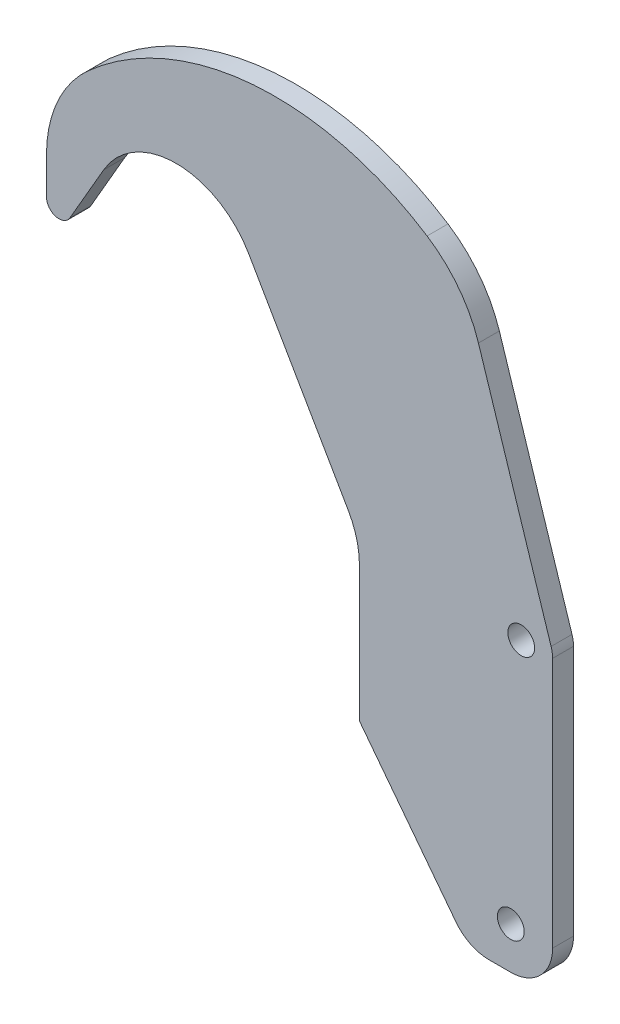
SolidWorks part; units mm, degrees
ref_plane "Front Plane" through (0, 0, 0) normal (0, 0, 1) x (1, 0, 0)
ref_plane "Top Plane" through (0, 0, 0) normal (0, 1, 0) x (1, 0, 0)
ref_plane "Right Plane" through (0, 0, 0) normal (1, 0, 0) x (0, 0, -1)
sketch "Sketch1" plane through (0, 0, 0) normal (0, 0, 1) x (1, 0, 0)
  line L0 (-10.9985, 23.8125) -> (-26.1215, -2.3812) construction
  line L1 (-15.123, -21.4313) -> (15.123, -21.4313) construction
  line L2 (26.1215, -2.3812) -> (10.9985, 23.8125) construction
  line L3 (10.9985, 23.8125) -> (26.1215, -2.3812)
  line L4 (-10.9985, 23.8125) -> (-16.1312, 14.9225)
  line L5 (-19.6859, 15.875) -> (-19.6859, 28.575)
  line L8 (57.15, -6.35) -> (57.15, -44.45)
  line L9 (50.8, -50.8) -> (47.4961, -50.8)
  line L15 (56.9223, -4.895) -> (44.1478, 34.9199)
  line L16 (27.823, -8.7312) -> (27.823, -29.2393)
  line L17 (27.823, -29.2393) -> (42.458, -48.3152)
  circle A0 centre (0, 0) radius 21.4313 construction
  arc A1 (10.9985, 23.8125) -> (-10.9985, 23.8125) centre (0, 17.4625) ccw construction
  arc A2 (-26.1215, -2.3812) -> (-15.123, -21.4313) centre (-15.123, -8.7313) ccw construction
  arc A3 (15.123, -21.4313) -> (26.1215, -2.3812) centre (15.123, -8.7312) ccw construction
  arc A4 (-10.9985, 23.8125) -> (10.9985, 23.8125) centre (0, 17.4625) cw
  arc A5 (26.1215, -2.3812) -> (27.823, -8.7312) centre (15.123, -8.7312) cw
  arc A6 (57.15, -6.35) -> (56.9223, -4.895) centre (52.3875, -6.35) ccw
  arc A9 (-19.6859, 15.875) -> (-16.1312, 14.9225) centre (-17.7809, 15.875) ccw
  arc A10 (50.8, -50.8) -> (57.15, -44.45) centre (50.8, -44.45) ccw
  arc A11 (42.458, -48.3152) -> (47.4961, -50.8) centre (47.4961, -44.45) ccw
  circle A12 centre (50.8, -44.45) radius 2.032
  circle A15 centre (52.3875, -6.35) radius 2.032
  arc A16 (-19.6859, 28.575) -> (44.1478, 34.9199) centre (14.9956, 3.9323) cw
  point P15 (43.8388, -44.45)
  point P26 (30.7767, -35.7857)
  point P29 (47.4961, -44.45)
  point P35 (32.6901, -34.829)
  point P36 (41.1461, -27.7493)
  point P37 (27.823, -29.2393)
  point P39 (27.823, 45.74)
  point P40 (44.1478, 34.9199)
  dimension "D2" = 12.7
  dimension "D3" = 9.525
  dimension "D1" = 42.8625
  dimension "D4" = 30
  dimension "D5" = 1.905
  dimension "D12" = 4.064
  dimension "D9" = 50.8
  dimension "D7" = 42.545
  dimension "D6" = 12.7
  dimension "D8" = 15.875
  dimension "D14" = 50.8
  dimension "D15" = 44.45
  dimension "D16" = 38.1
extrude "Boss-Extrude1" add sketch "Sketch1" along normal mid plane 3.175
fillet "Fillet1" radius 19.05 2 edges at (-19.6859, 28.575, 0) (44.1478, 34.9199, 0)
